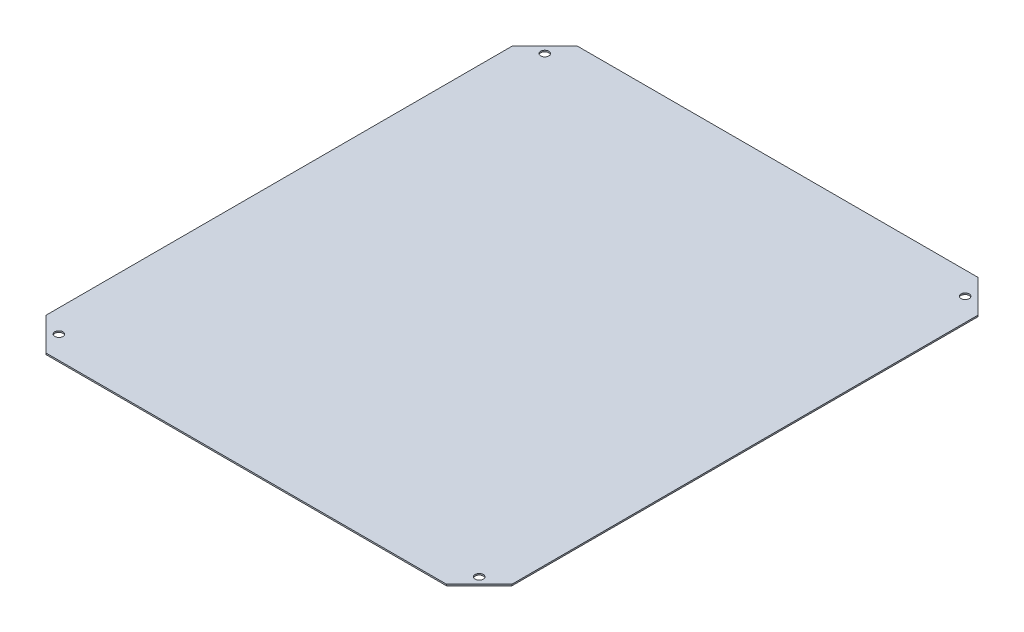
SolidWorks part; units mm, degrees
ref_plane "Front Plane" through (0, 0, 0) normal (0, 0, 1) x (1, 0, 0)
ref_plane "Top Plane" through (0, 0, 0) normal (0, 1, 0) x (1, 0, 0)
ref_plane "Right Plane" through (0, 0, 0) normal (1, 0, 0) x (0, 0, -1)
sketch "Sketch3" plane through (0, 0, 0) normal (0, 1, 0) x (1, 0, 0)
  line L4 (-57.0395, 93.017) -> (57.0395, 93.017)
  line L5 (57.0395, 93.017) -> (110.0725, 146.05)
  line L14 (110.0725, 146.05) -> (128.033, 128.0895)
  line L15 (128.033, 128.0895) -> (75, 75.0565)
  line L16 (75, 75.0565) -> (75, 0)
  line L17 (0, 0) -> (0, 93.017) construction
  line L18 (0, 0) -> (75, 0) construction
  line L19 (-75, 75.0565) -> (-75, -75.0565)
  line L20 (-128.033, 128.0895) -> (-75, 75.0565)
  line L21 (-110.0725, 146.05) -> (-128.033, 128.0895)
  line L22 (-57.0395, 93.017) -> (-110.0725, 146.05)
  line L23 (-57.0395, -93.017) -> (-110.0725, -146.05)
  line L24 (-110.0725, -146.05) -> (-128.033, -128.0895)
  line L25 (-128.033, -128.0895) -> (-75, -75.0565)
  line L26 (75, -75.0565) -> (75, 0)
  line L27 (128.033, -128.0895) -> (75, -75.0565)
  line L28 (110.0725, -146.05) -> (128.033, -128.0895)
  line L29 (57.0395, -93.017) -> (110.0725, -146.05)
  line L30 (-57.0395, -93.017) -> (57.0395, -93.017)
  point P5 (75, 37.5282)
  point P18 (-75, 0)
  dimension "D1" = 25.4
  dimension "D2" = 75
  dimension "D4" = 75
  dimension "D5" = 135
  dimension "D3" = 292.1
extrude "Sheet" add sketch "Sketch3" along normal blind 0.7937
fillet "Fillet1" radius 50 8 edges at (-75, 0.3969, 75.0565) (-57.0395, 0.3969, 93.017) (75, 0.3969, 75.0565) (57.0395, 0.3969, 93.017) (57.0395, 0.3969, -93.017) (75, 0.3969, -75.0565) (-75, 0.3969, -75.0565) (-57.0395, 0.3969, -93.017)
hole_wizard "M4 Clearance Hole1" positions "Sketch4" profile "Sketch5" hole size "M4" standard "ANSI Metric" end condition through all
sketch "Sketch4" plane through (0, 0.7937, 0) normal (0, 1, 0) x (1, 0, 0)
  line L0 (119.0528, 137.0697) -> (55.6644, 73.6814) construction
  line L1 (128.033, 128.0895) -> (110.0725, 146.05) construction
  line L2 (36.3288, 93.017) -> (75, 54.3458) construction
  point P0 (115.5172, 133.5342)
  point P15 (55.6644, 73.6814)
  dimension "D1" = 5
sketch "Sketch5" plane through (115.5172, 0.7937, -133.5342) normal (1, 0, 0) x (0, 0, 1)
  line L0 (0, 0) -> (0, 0.7937)
  line L1 (0, 0.7937) -> (2.25, 0.7937)
  line L2 (2.25, 0.7937) -> (2.25, 0)
  line L5 (2.25, 0) -> (0, 0)
  line L11 (0, -6.35) -> (0, 107.95) construction
  dimension "Thru Hole Dia." = 4.5
  dimension "Thru Hole Depth" = 0.7937
pattern_linear "HolePattern" [suppressed] count 6 spacing 10 of bodies 109
mirror "PatternMirror1" [suppressed] about plane through (0, 0, 0) normal (0, 0, 1)
mirror "PatternMirror2" [suppressed] about plane through (0, 0, 0) normal (1, 0, 0)
mirror "SingleHoleMirror1" about plane through (0, 0, 0) normal (0, 0, 1) of "M4 Clearance Hole1"
mirror "SingleHoleMirror2" about plane through (0, 0, 0) normal (1, 0, 0) of "SingleHoleMirror1"
sketch "Sketch6" plane through (0, 0.7937, 0) normal (0, 1, 0) x (1, 0, 0)
  line L0 (-128.033, 128.0895) -> (-128.033, -128.0895)
  line L2 (-89.6447, -89.7011) -> (-128.033, -128.0895) construction
  line L3 (-110.0725, -146.05) -> (110.0725, -146.05)
  line L4 (128.033, 128.0895) -> (128.033, -128.0895)
  line L5 (89.6447, 89.7011) -> (128.033, 128.0895) construction
  line L6 (75, -54.3458) -> (75, 54.3458) construction
  line L7 (128.033, -128.0895) -> (89.6447, -89.7011) construction
  line L8 (71.6841, -107.6617) -> (110.0725, -146.05) construction
  line L9 (-36.3288, -93.017) -> (36.3288, -93.017) construction
  line L10 (-110.0725, -146.05) -> (-71.6841, -107.6617) construction
  line L11 (-75, 54.3458) -> (-75, -54.3458) construction
  line L12 (-128.033, 128.0895) -> (-89.6447, 89.7011) construction
  line L13 (89.6447, 89.7011) -> (128.033, 128.0895)
  line L14 (75, -54.3458) -> (75, 54.3458)
  line L15 (128.033, -128.0895) -> (89.6447, -89.7011)
  line L16 (71.6841, -107.6617) -> (110.0725, -146.05)
  line L17 (-36.3288, -93.017) -> (36.3288, -93.017)
  line L18 (-110.0725, -146.05) -> (-71.6841, -107.6617)
  line L19 (-89.6447, -89.7011) -> (-128.033, -128.0895)
  line L20 (-75, 54.3458) -> (-75, -54.3458)
  line L21 (-128.033, 128.0895) -> (-89.6447, 89.7011)
  arc A0 (89.6447, 89.7011) -> (75, 54.3458) centre (125, 54.3458) ccw construction
  arc A1 (75, -54.3458) -> (89.6447, -89.7011) centre (125, -54.3458) ccw construction
  arc A2 (71.6841, -107.6617) -> (36.3288, -93.017) centre (36.3288, -143.017) ccw construction
  arc A3 (-36.3288, -93.017) -> (-71.6841, -107.6617) centre (-36.3288, -143.017) ccw construction
  arc A4 (-89.6447, -89.7011) -> (-75, -54.3458) centre (-125, -54.3458) ccw construction
  arc A5 (-75, 54.3458) -> (-89.6447, 89.7011) centre (-125, 54.3458) ccw construction
  arc A6 (89.6447, 89.7011) -> (75, 54.3458) centre (125, 54.3458) ccw
  arc A7 (75, -54.3458) -> (89.6447, -89.7011) centre (125, -54.3458) ccw
  arc A8 (71.6841, -107.6617) -> (36.3288, -93.017) centre (36.3288, -143.017) ccw
  arc A9 (-36.3288, -93.017) -> (-71.6841, -107.6617) centre (-36.3288, -143.017) ccw
  arc A10 (-89.6447, -89.7011) -> (-75, -54.3458) centre (-125, -54.3458) ccw
  arc A11 (-75, 54.3458) -> (-89.6447, 89.7011) centre (-125, 54.3458) ccw
extrude "FullSheetSideFlaps" add sketch "Sketch6" against normal up to surface (0.7937 mm away) up to face at (-115.5172, 0, -131.2842)
sketch "Sketch8" [suppressed] plane through (0, 0.7937, 0) normal (0, 1, 0) x (1, 0, 0)
  line L0 (-128.033, 128.0895) -> (-128.033, -128.0895)
  line L1 (-128.033, -128.0895) -> (-106.5774, -49.6627)
  line L2 (-103.033, -23.2749) -> (-103.033, 23.2749)
  line L3 (-106.5774, 49.6627) -> (-128.033, 128.0895)
  line L4 (0, -0.4366) -> (0, 0.4366) construction
  line L5 (106.5774, 49.6627) -> (128.033, 128.0895)
  line L6 (103.033, -23.2749) -> (103.033, 23.2749)
  line L7 (128.033, -128.0895) -> (106.5774, -49.6627)
  line L8 (128.033, 128.0895) -> (128.033, -128.0895)
  line L9 (-110.0725, -146.05) -> (110.0725, -146.05)
  line L10 (110.0725, -146.05) -> (39.1925, -121.05)
  line L11 (39.1925, -121.05) -> (-39.1925, -121.05)
  line L12 (-39.1925, -121.05) -> (-110.0725, -146.05)
  arc A0 (-103.033, 23.2749) -> (-106.5774, 49.6627) centre (-203.033, 23.2749) ccw
  arc A1 (-106.5774, -49.6627) -> (-103.033, -23.2749) centre (-203.033, -23.2749) ccw
  arc A2 (106.5774, -49.6627) -> (103.033, -23.2749) centre (203.033, -23.2749) cw
  arc A3 (103.033, 23.2749) -> (106.5774, 49.6627) centre (203.033, 23.2749) cw
  point P11 (-103.033, 0)
  point P27 (0, -121.05)
  dimension "D1" = 100
  dimension "D2" = 100
  dimension "D3" = 25
  dimension "D4" = 25
extrude "ReducedFlap" [suppressed] cut sketch "Sketch8" against normal up to next
sketch "Sketch9" plane through (0, 0.7937, 0) normal (0, 1, 0) x (1, 0, 0)
  line L0 (110.0725, 146.05) -> (71.6841, 107.6617) construction
  line L1 (36.3288, 93.017) -> (-36.3288, 93.017) construction
  line L2 (-71.6841, 107.6617) -> (-110.0725, 146.05) construction
  line L3 (110.0725, 146.05) -> (71.6841, 107.6617)
  line L4 (36.3288, 93.017) -> (-36.3288, 93.017)
  line L5 (-71.6841, 107.6617) -> (-110.0725, 146.05)
  line L6 (-110.0725, 146.05) -> (110.0725, 146.05)
  arc A0 (36.3288, 93.017) -> (71.6841, 107.6617) centre (36.3288, 143.017) ccw construction
  arc A1 (-71.6841, 107.6617) -> (-36.3288, 93.017) centre (-36.3288, 143.017) ccw construction
  arc A2 (36.3288, 93.017) -> (71.6841, 107.6617) centre (36.3288, 143.017) ccw
  arc A3 (-71.6841, 107.6617) -> (-36.3288, 93.017) centre (-36.3288, 143.017) ccw
extrude "CloseCannulusSide" add sketch "Sketch9" against normal up to surface (0.7937 mm away) up to face at (0, 0, -32.8604)
sketch "Sketch10" [suppressed] plane through (0, 0.7937, 0) normal (0, 1, 0) x (1, 0, 0)
  line L0 (128.033, 128.0895) -> (110.0725, 146.05) construction
  line L1 (110.0725, -146.05) -> (128.033, -128.0895) construction
  line L2 (128.033, -128.0895) -> (128.033, 128.0895) construction
  line L3 (-110.0725, -146.05) -> (110.0725, -146.05) construction
  line L4 (-128.033, -128.0895) -> (-110.0725, -146.05) construction
  line L5 (-128.033, 128.0895) -> (-128.033, -128.0895) construction
  line L6 (-110.0725, 146.05) -> (-128.033, 128.0895) construction
  line L7 (110.0725, 146.05) -> (-110.0725, 146.05) construction
  line L8 (128.033, 128.0895) -> (110.0725, 146.05)
  line L9 (110.0725, -146.05) -> (128.033, -128.0895)
  line L10 (128.033, -128.0895) -> (128.033, 128.0895)
  line L11 (-110.0725, -146.05) -> (110.0725, -146.05)
  line L12 (-128.033, -128.0895) -> (-110.0725, -146.05)
  line L13 (-128.033, 128.0895) -> (-128.033, -128.0895)
  line L14 (-110.0725, 146.05) -> (-128.033, 128.0895)
  line L15 (110.0725, 146.05) -> (-110.0725, 146.05)
  line L17 (-178.833, -196.85) -> (178.833, -196.85)
  line L18 (-178.833, -196.85) -> (-178.833, 196.85)
  line L19 (-178.833, 196.85) -> (178.833, 196.85)
  line L20 (178.833, -196.85) -> (178.833, 196.85)
  line L21 (-178.833, -196.85) -> (178.833, 196.85) construction
  line L22 (-178.833, 196.85) -> (178.833, -196.85) construction
  point P4 (0, 0)
  dimension "D1" = 50.8
  dimension "D2" = 50.8
extrude "ExcessAllSides" [suppressed] add sketch "Sketch10" against normal up to surface (0.7937 mm away) up to face at (0, 0, 0)
equation "\"SheetLength\"= 258"
equation "\"D2@Sketch3\"=\"SheetWidth\" / 2 - \"SheetEdgeOffset\""
equation "\"SheetWidth\"=200"
equation "\"TabLength\"=75"
equation "\"D4@Sketch3\"= \"TabLength\""
equation "\"SheetEdgeOffset\"= 25mm"
equation "\"RawSheetSize\"=304.8"
equation "\"D3@Sketch3\"=\"RawSheetSize\" - \"SlopForLaserCutting\""
equation "\"SlopForLaserCutting\"= 0.5in"
equation "\"FlapDepth\"=25"
equation "\"D3@Sketch8\"=\"FlapDepth\""
equation "\"D4@Sketch8\"=\"FlapDepth\""
equation "\"D1@Sketch10\"=2in"
equation "\"D2@Sketch10\"=2in"
